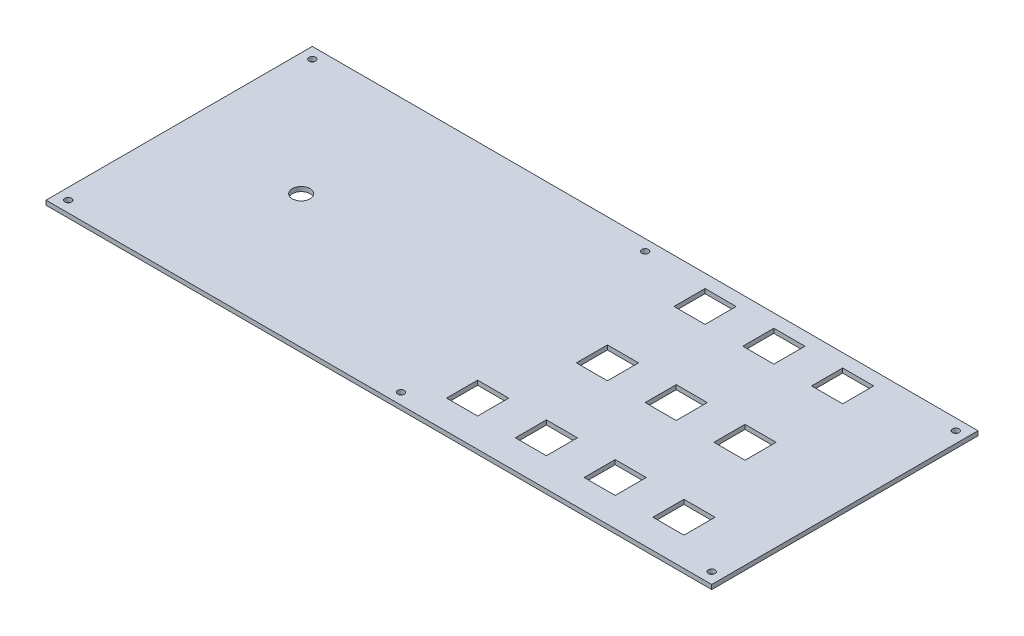
SolidWorks part; units mm, degrees
ref_plane "Front" through (0, 0, 0) normal (0, 0, 1) x (1, 0, 0)
ref_plane "Top" through (0, 0, 0) normal (0, 1, 0) x (1, 0, 0)
ref_plane "Right" through (0, 0, 0) normal (1, 0, 0) x (0, 0, -1)
sketch "Sketch1" plane through (0, 0, 0) normal (0, 1, 0) x (1, 0, 0)
  line L0 (17.5, -33) -> (31.5, -33)
  line L1 (-150, 60) -> (150, 60)
  line L2 (-150, 60) -> (-150, -60)
  line L3 (-150, -60) -> (150, -60)
  line L4 (150, 60) -> (150, -60)
  line L5 (-150, 60) -> (150, -60) construction
  line L6 (-150, -60) -> (150, 60) construction
  line L7 (33, 10) -> (47, 10)
  line L8 (33, 10) -> (33, -4)
  line L9 (33, -4) -> (47, -4)
  line L10 (47, 10) -> (47, -4)
  line L11 (33, 10) -> (47, -4) construction
  line L12 (33, -4) -> (47, 10) construction
  line L13 (30.5, 19.5) -> (49.5, 19.5) construction
  line L14 (30.5, 19.5) -> (30.5, -13.5) construction
  line L15 (30.5, -13.5) -> (49.5, -13.5) construction
  line L16 (49.5, 19.5) -> (49.5, -13.5) construction
  line L17 (30.5, 19.5) -> (49.5, -13.5) construction
  line L18 (30.5, -13.5) -> (49.5, 19.5) construction
  line L19 (17.5, -33) -> (17.5, -47)
  line L20 (17.5, -47) -> (31.5, -47)
  line L21 (31.5, -33) -> (31.5, -47)
  line L22 (17.5, -33) -> (31.5, -47) construction
  line L23 (17.5, -47) -> (31.5, -33) construction
  line L24 (15, -23.5) -> (34, -23.5) construction
  line L25 (15, -23.5) -> (15, -56.5) construction
  line L26 (15, -56.5) -> (34, -56.5) construction
  line L27 (34, -23.5) -> (34, -56.5) construction
  line L28 (15, -23.5) -> (34, -56.5) construction
  line L29 (15, -56.5) -> (34, -23.5) construction
  line L30 (64, 10) -> (64, -4)
  line L31 (64, 10) -> (78, 10)
  line L32 (78, 10) -> (78, -4)
  line L33 (64, -4) -> (78, -4)
  line L34 (95, 10) -> (95, -4)
  line L35 (95, 10) -> (109, 10)
  line L36 (109, 10) -> (109, -4)
  line L37 (95, -4) -> (109, -4)
  line L38 (48.5, -33) -> (62.5, -33)
  line L39 (62.5, -33) -> (62.5, -47)
  line L40 (48.5, -47) -> (62.5, -47)
  line L41 (48.5, -33) -> (48.5, -47)
  line L42 (79.5, -33) -> (93.5, -33)
  line L43 (93.5, -33) -> (93.5, -47)
  line L44 (79.5, -47) -> (93.5, -47)
  line L45 (79.5, -33) -> (79.5, -47)
  line L46 (110.5, -33) -> (124.5, -33)
  line L47 (124.5, -33) -> (124.5, -47)
  line L48 (110.5, -47) -> (124.5, -47)
  line L49 (110.5, -33) -> (110.5, -47)
  line L50 (31.5, -47) -> (48.5, -47) construction
  line L51 (33, 54) -> (47, 54)
  line L52 (33, 54) -> (33, 40)
  line L53 (33, 40) -> (47, 40)
  line L54 (47, 54) -> (47, 40)
  line L55 (33, 54) -> (47, 40) construction
  line L56 (33, 40) -> (47, 54) construction
  line L57 (23.5, 56.5) -> (56.5, 56.5) construction
  line L58 (23.5, 56.5) -> (23.5, 37.5) construction
  line L59 (23.5, 37.5) -> (56.5, 37.5) construction
  line L60 (56.5, 56.5) -> (56.5, 37.5) construction
  line L61 (23.5, 56.5) -> (56.5, 37.5) construction
  line L62 (23.5, 37.5) -> (56.5, 56.5) construction
  line L63 (64, 54) -> (64, 40)
  line L64 (64, 54) -> (78, 54)
  line L65 (78, 54) -> (78, 40)
  line L66 (64, 40) -> (78, 40)
  line L67 (95, 54) -> (95, 40)
  line L68 (95, 54) -> (109, 54)
  line L69 (109, 54) -> (109, 40)
  line L70 (95, 40) -> (109, 40)
  line L71 (-45, 0) -> (-45, -60) construction
  line L72 (0, 0) -> (0, 35.0503) construction
  line L73 (0, 0) -> (-35.7443, 0) construction
  line L74 (0, 60) -> (0, -60) construction
  circle A0 centre (-95, 0) radius 50 construction
  circle A1 centre (-95, 0) radius 4
  circle A2 centre (-145, 55) radius 1.5
  circle A3 centre (145, 55) radius 1.5
  circle A4 centre (-145, -55) radius 1.5
  circle A5 centre (145, -55) radius 1.5
  circle A6 centre (5, 55) radius 1.5
  circle A7 centre (5, -55) radius 1.5
  point P0 (0, 0)
  point P6 (40, 3)
  point P11 (40, 3)
  point P17 (24.5, -40)
  point P22 (24.5, -40)
  point P48 (40, 47)
  point P49 (-150, 0)
  point P51 (40, 47)
  point P59 (40, -47)
  point P88 (0, -60)
  dimension "D21" = 100
  dimension "D26" = 8
  dimension "D29" = 3
  dimension "D1" = 300
  dimension "D2" = 120
  dimension "D3" = 33
  dimension "D4" = 19
  dimension "D5" = 14
  dimension "D6" = 33
  dimension "D7" = 19
  dimension "D8" = 14
  dimension "D9" = 43
  dimension "D10" = 15.5
  dimension "D12" = 4
  dimension "D13" = 31
  dimension "D14" = 31
  dimension "D15" = 33
  dimension "D16" = 19
  dimension "D17" = 14
  dimension "D18" = 3
  dimension "D19" = 55
  dimension "D20" = 31
  dimension "D22" = 18
  dimension "D23" = 3.5
  dimension "D24" = 3.5
  dimension "D25" = 60
  dimension "D27" = 5
  dimension "D28" = 5
  dimension "D31" = 5
  dimension "D11" = 3
  dimension "D30" = 2
extrude "Boss-Extrude1" add sketch "Sketch1" along normal blind 2
